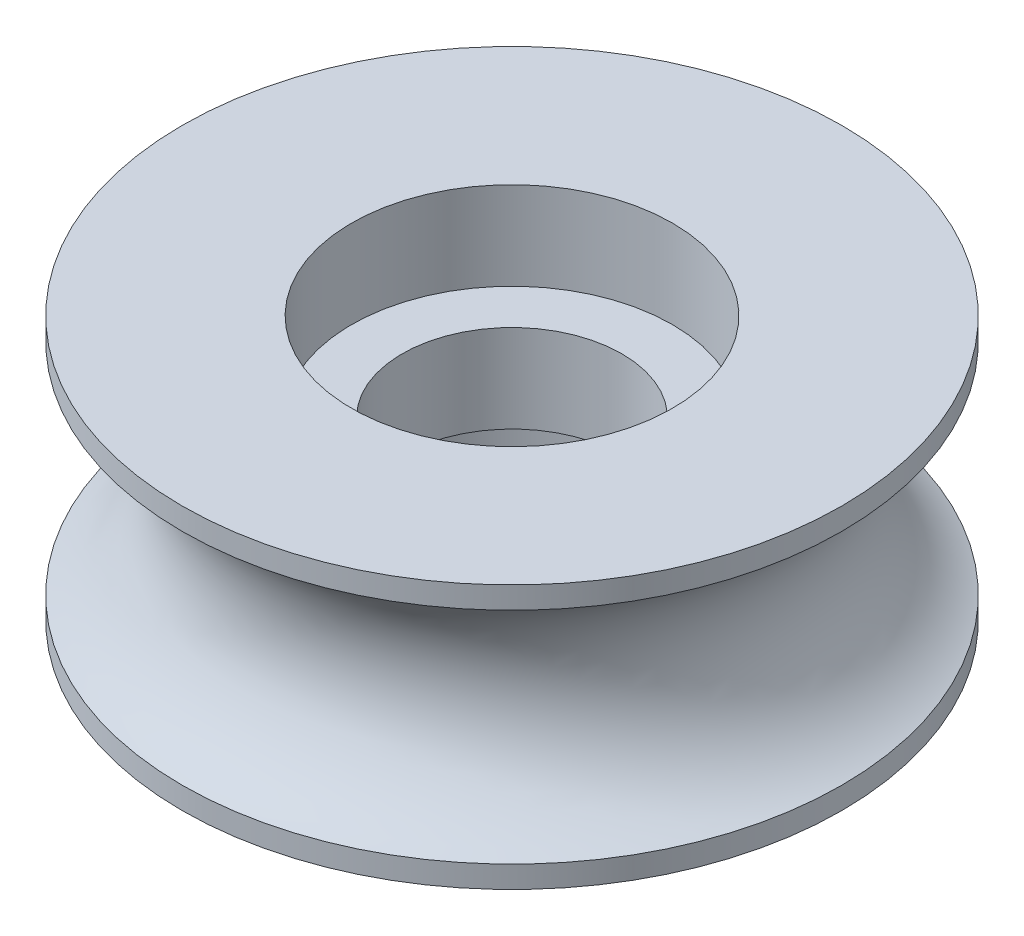
SolidWorks part; units mm, degrees
ref_plane "Ebene vorne" through (0, 0, 0) normal (0, 0, 1) x (1, 0, 0)
ref_plane "Ebene oben" through (0, 0, 0) normal (0, 1, 0) x (1, 0, 0)
ref_plane "Ebene rechts" through (0, 0, 0) normal (1, 0, 0) x (0, 0, -1)
sketch "Sketch1" plane through (0, 0, 0) normal (0, 0, 1) x (1, 0, 0)
  line L0 (0, -6.6295) -> (0, 11.8219) construction
  line L1 (-3.65, 0) -> (-7.5, 0)
  line L2 (-7.5, 0) -> (-7.5, 0.5)
  line L3 (-7.5, 6) -> (-3.65, 6)
  line L4 (-3.65, 6) -> (-3.65, 4)
  line L5 (-3.65, 2) -> (-3.65, 0)
  line L7 (-7.5, 5.5) -> (-7.5, 6)
  line L8 (-9.5365, 3) -> (-0.4374, 3) construction
  line L10 (-3.65, 2) -> (-2.5, 2)
  line L11 (-2.5, 2) -> (-2.5, 4)
  line L12 (-2.5, 4) -> (-3.65, 4)
  arc A1 (-7.5, 5.5) -> (-7.5, 0.5) centre (-8.5198, 3) cw
  dimension "D4" = 2.7
  dimension "D1" = 7.3
  dimension "D2" = 6
  dimension "D3" = 5
  dimension "D5" = 15
  dimension "D7" = 5
  dimension "D8" = 2
revolve "Revolve1" add sketch "Sketch1" angle 360 about L0
